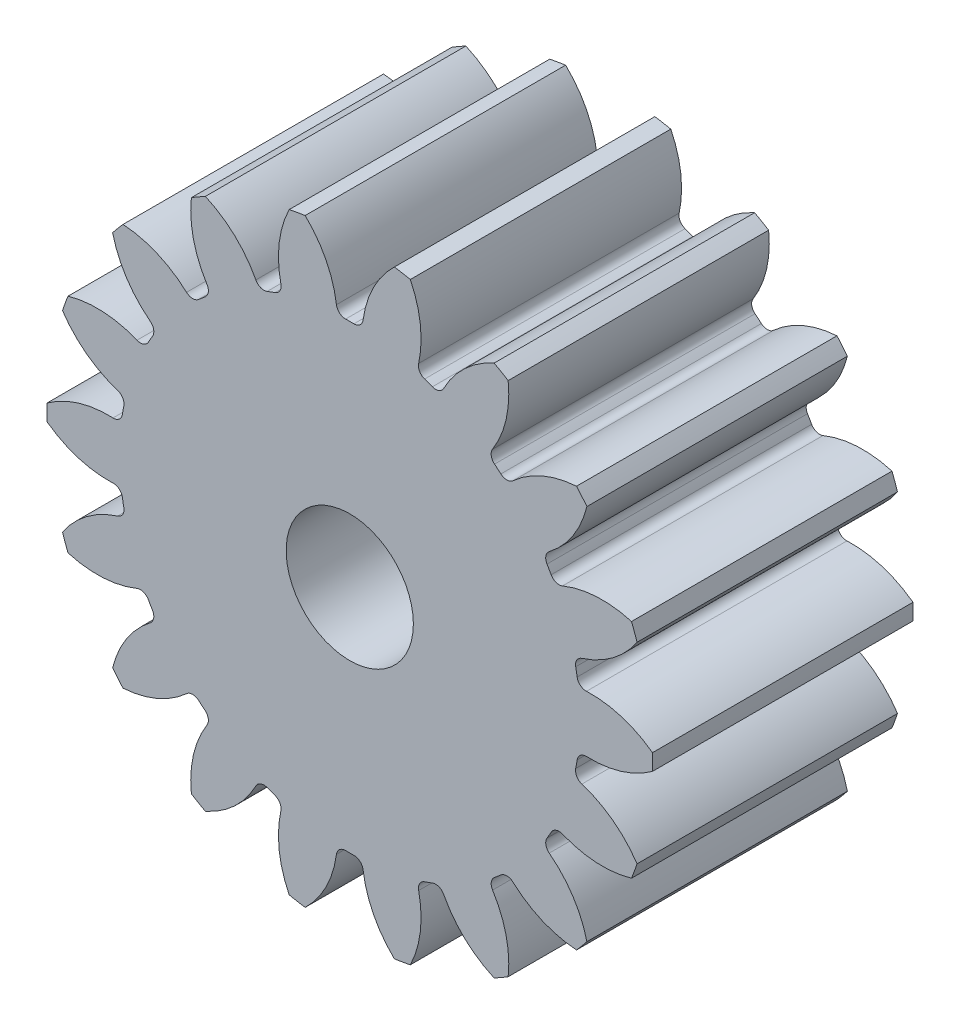
SolidWorks part; units mm, degrees
ref_plane "Front Plane" through (0, 0, 0) normal (0, 0, 1) x (1, 0, 0)
ref_plane "Top Plane" through (0, 0, 0) normal (0, 1, 0) x (1, 0, 0)
ref_plane "Right Plane" through (0, 0, 0) normal (1, 0, 0) x (0, 0, -1)
sketch "Sketch1" plane through (0, 0, 0) normal (0, 0, 1) x (1, 0, 0)
  circle A0 centre (0, 0) radius 4.5
  circle A1 centre (0, 0) radius 5
  circle A2 centre (0, 0) radius 3.8
  dimension "D1" = 9
  dimension "D2" = 0.5
  dimension "D3" = 1.2
extrude "Boss-Extrude1" add sketch "Sketch1" along normal mid plane 4.3 contours A1
sketch "Gear Profile" plane through (0, 0, 0) normal (0, 0, 1) x (1, 0, 0)
  line L0 (0, 0) -> (0, 5) construction
  line L1 (-0.3922, 4.4829) -> (0.3922, 4.4829) construction
  line L2 (-0.2069, 3.7944) -> (0, 0) construction
  line L3 (0, 3.7131) -> (-0.8748, 5.43) construction
  line L4 (0, 0) -> (0.8682, 4.924) construction
  line L5 (0.3922, 4.4829) -> (1.1647, 4.3467) construction
  circle A0 centre (0, 0) radius 5 construction
  arc A1 (-1.3626, 5.3285) -> (-0.2069, 3.7944) centre (-1.9277, 3.7005) cw
  arc A2 (1.3626, 5.3285) -> (0.2069, 3.7944) centre (1.9277, 3.7005) ccw
  circle A3 centre (0, 0) radius 3.8 construction
  arc A4 (0.2069, 3.7944) -> (-0.2069, 3.7944) centre (0, 0) ccw
  circle A5 centre (0, 0) radius 4.5 construction
  circle A6 centre (0, 0) radius 5 construction
  circle A7 centre (0, 0) radius 5.5
  arc A8 (1.3626, 5.3285) -> (-1.3626, 5.3285) centre (0, 0) ccw
  dimension "D2" = 27
  dimension "D3" = 10
  dimension "D1" = 0.5
extrude "Cut-Extrude1" cut sketch "Gear Profile" against normal through all both and the other way through all
fillet "Fillet1" radius 0.15 2 edges at (0.2069, 3.7944, 0) (-0.2069, 3.7944, 0)
ref_axis "Axis1" through (0, 0, -2.75) along (0, 0, 1)
pattern_circular "CirPattern1" count 18 over 360 about axis through (0, 0, -2.75) along (0, 0, 1) of "Fillet1", "Cut-Extrude1"
sketch "Sketch2" plane through (0, 0, 0) normal (0, 0, 1) x (1, 0, 0)
  circle A0 centre (0, 0) radius 1.05
  dimension "D1" = 2.1
extrude "Cut-Extrude2" cut sketch "Sketch2" against normal through all both and the other way through all
sketch "Sketch3" plane through (0, 0, 0) normal (0, 0, 1) x (1, 0, 0)
  point P0 (0, 0)
equation "\"Module\"= 0.5mm"
equation "\"Number of Teeth\"= 18"
equation "\"D1@Sketch1\"=\"Module\" * \"Number of Teeth\""
equation "\"D2@Sketch1\"=\"Module\""
equation "\"D3@Sketch1\"=\"Module\" * if( \"Module\"=>1.25,2.25,2.4)"
equation "\"Width\"= 4.3mm"
equation "\"D1@Boss-Extrude1\"=\"Width\""
equation "\"Pressure Angle\"= 27deg"
equation "\"D2@Gear Profile\"=\"Pressure Angle\""
equation "\"D3@Gear Profile\"=180 / \"Number of Teeth\""
equation "\"D1@Fillet1\"=0.3*\"Module\""
equation "\"D1@CirPattern1\"=\"Number of Teeth\""
equation "\"Hole Diammeter\"=2"
equation "\"D1@Sketch2\"=\"Hole Diammeter\"+0.1mm"
